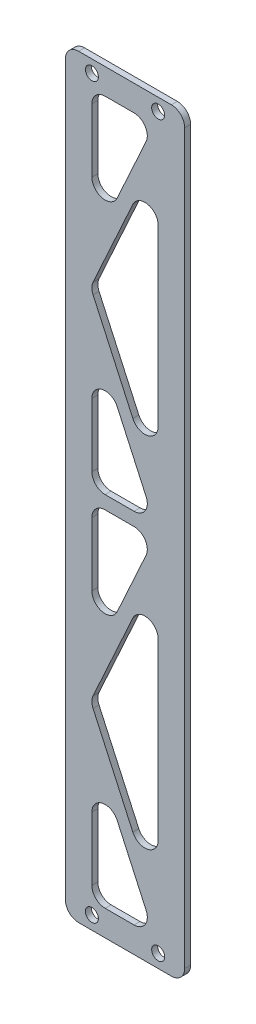
SolidWorks part; units mm, degrees
material "6061-T6 (SS)"
ref_plane "Front Plane" through (0, 0, 0) normal (0, 0, 1) x (1, 0, 0)
ref_plane "Top Plane" through (0, 0, 0) normal (0, 1, 0) x (1, 0, 0)
ref_plane "Right Plane" through (0, 0, 0) normal (1, 0, 0) x (0, 0, -1)
sketch "Sketch1" plane through (0, 0, 0) normal (0, 0, 1) x (1, 0, 0)
  line L0 (-5.08, -5.08) -> (30.48, -5.08)
  line L1 (35.56, 0) -> (35.56, 279.4)
  line L2 (30.48, 284.48) -> (-5.08, 284.48)
  line L3 (-10.16, 279.4) -> (-10.16, 0)
  line L6 (16.1606, 274.32) -> (0, 274.32)
  line L7 (0, 274.32) -> (0, 107.6181)
  line L10 (28.1496, 4.7625) -> (-49966.223, 4.7625) construction
  line L11 (20.7828, 11.9499) -> (9.7022, 36.253)
  line L12 (1052.7568, 4.7625) -> (24.0598, 4.7625) construction
  line L14 (5.08, 4.7625) -> (16.1606, 4.7625)
  line L15 (0.4578, 68.7744) -> (15.6978, 35.3485)
  line L17 (0, 34.1456) -> (0, 9.8425)
  line L18 (0, 70.8819) -> (-50000, 70.8819) construction
  line L19 (0.4578, 72.9893) -> (15.6978, 106.4153)
  line L20 (0, 107.6181) -> (0, 131.9213)
  line L21 (20.7828, 129.8138) -> (9.7022, 105.5107)
  line L22 (5.08, 137.0013) -> (16.1606, 137.0013)
  line L23 (12.7, -5.08) -> (12.7, 49994.92) construction
  line L24 (-10.16, 139.5413) -> (-50010.16, 139.5412) construction
  line L25 (30.48, -5.3975) -> (-5.08, -5.3975)
  line L26 (35.56, 279.0825) -> (35.56, -0.3175)
  line L27 (-5.08, 284.1625) -> (30.48, 284.1625)
  line L28 (-10.16, -0.3175) -> (-10.16, 279.0825)
  line L29 (0.4578, 210.3081) -> (15.6978, 243.734)
  line L30 (0.4578, 206.0932) -> (15.6978, 172.6672)
  line L31 (20.7828, 149.2687) -> (9.7022, 173.5718)
  line L32 (5.08, 142.0813) -> (16.1606, 142.0813)
  line L33 (0, 171.4644) -> (0, 147.1612)
  line L34 (0, 244.9369) -> (0, 269.24)
  line L35 (20.7828, 267.1326) -> (9.7022, 242.8295)
  line L36 (5.08, 274.32) -> (16.1606, 274.32)
  line L37 (25.4, 174.7746) -> (25.4, 241.6266)
  line L38 (25.4, 104.3079) -> (25.4, 37.4559)
  arc A24 (-5.08, 284.48) -> (-10.16, 279.4) centre (-5.08, 279.4) ccw
  arc A25 (35.56, 279.4) -> (30.48, 284.48) centre (30.48, 279.4) ccw
  arc A26 (30.48, -5.08) -> (35.56, 0) centre (30.48, 0) ccw
  arc A27 (-5.08, -5.08) -> (-10.16, 0) centre (-5.08, 0) cw
  arc A28 (0.4578, 72.9893) -> (0.4578, 68.7744) centre (5.08, 70.8819) ccw
  arc A29 (15.6978, 35.3485) -> (25.4, 37.4559) centre (20.32, 37.4559) ccw
  arc A30 (5.08, 4.7625) -> (0, 9.8425) centre (5.08, 9.8425) cw
  arc A31 (9.7022, 36.253) -> (0, 34.1456) centre (5.08, 34.1456) ccw
  arc A32 (20.7828, 11.9499) -> (16.1606, 4.7625) centre (16.1606, 9.8425) cw
  arc A33 (15.6978, 106.4153) -> (25.4, 104.3079) centre (20.32, 104.3079) cw
  arc A34 (9.7022, 105.5107) -> (0, 107.6181) centre (5.08, 107.6181) cw
  arc A35 (5.08, 137.0013) -> (0, 131.9213) centre (5.08, 131.9213) ccw
  arc A36 (20.7828, 129.8138) -> (16.1606, 137.0013) centre (16.1606, 131.9213) ccw
  arc A37 (15.6978, 172.6672) -> (25.4, 174.7746) centre (20.32, 174.7746) ccw
  arc A38 (35.56, -0.3175) -> (30.48, -5.3975) centre (30.48, -0.3175) cw
  arc A39 (30.48, 284.1625) -> (35.56, 279.0825) centre (30.48, 279.0825) cw
  arc A40 (-5.08, -5.3975) -> (-10.16, -0.3175) centre (-5.08, -0.3175) cw
  arc A41 (-5.08, 284.1625) -> (-10.16, 279.0825) centre (-5.08, 279.0825) ccw
  arc A42 (15.6978, 243.734) -> (25.4, 241.6266) centre (20.32, 241.6266) cw
  arc A43 (0.4578, 206.0932) -> (0.4578, 210.3081) centre (5.08, 208.2006) cw
  arc A44 (9.7022, 173.5718) -> (0, 171.4644) centre (5.08, 171.4644) ccw
  arc A45 (20.7828, 149.2687) -> (16.1606, 142.0813) centre (16.1606, 147.1612) cw
  arc A46 (5.08, 142.0813) -> (0, 147.1612) centre (5.08, 147.1612) cw
  arc A47 (9.7022, 242.8295) -> (0, 244.9369) centre (5.08, 244.9369) cw
  arc A48 (5.08, 274.32) -> (0, 269.24) centre (5.08, 269.24) ccw
  arc A49 (20.7828, 267.1326) -> (16.1606, 274.32) centre (16.1606, 269.24) ccw
  circle A50 centre (0, 279.4) radius 2.4892
  circle A51 centre (25.4, 279.4) radius 2.4892
  circle A52 centre (25.4, 0) radius 2.4892
  circle A53 centre (0, 0) radius 2.4892
  point P55 (0, 57.533)
  point P80 (12.7, -5.08)
  dimension "D8" = 5.08
  dimension "D9" = 5.08
  dimension "D1" = 5.08
  dimension "D2" = 5.08
  dimension "D3" = 10.16
  dimension "D4" = 22.86
  dimension "D5" = 5.08
  dimension "D6" = 10.16
  dimension "D7" = 10.16
  dimension "D10" = 134.7788
  dimension "D12" = 11.0806
  dimension "D13" = 2.54
extrude "Boss-Extrude1" add sketch "Sketch1" along normal blind 2.286 contours L27 A41 L3 A27 L0 A26 L1 A39 A49 L35 A47 A43 L29 A42 L37 A37 L30 A44 L31 A45 L32 A46 A35 L22 A36 L21 A34 L7 L6 region at (12.7244, 139.4515, 0)
sketch "Sketch2" [suppressed] plane through (0, 0, 0) normal (0, 0, 1) x (1, 0, 0)
  line L0 (-10.16, 139.5413) -> (35.56, 139.5413) construction
  line L1 (-10.16, 279.0825) -> (-10.16, 0) construction
  line L2 (35.56, 0) -> (35.56, 279.0825) construction
  circle A0 centre (11.1513, 150.9931) radius 2.54
  circle A1 centre (11.1513, 265.8166) radius 2.54
  circle A2 centre (17.3447, 224.9694) radius 2.54
  circle A3 centre (17.3447, 191.4897) radius 2.54
  circle A4 centre (6.8102, 162.3333) radius 2.54
  circle A5 centre (6.8102, 254.7484) radius 2.54
  circle A6 centre (11.1513, 13.2659) radius 2.54
  circle A7 centre (6.8102, 24.3341) radius 2.54
  circle A8 centre (17.3447, 54.1131) radius 2.54
  circle A9 centre (17.3447, 87.5928) radius 2.54
  circle A10 centre (11.1513, 128.0894) radius 2.54
  circle A11 centre (6.8102, 116.7492) radius 2.54
  dimension "D1" = 5.08
fillet "Fillet1" radius 5.08 1 edges at (0, 274.32, 1.143)
